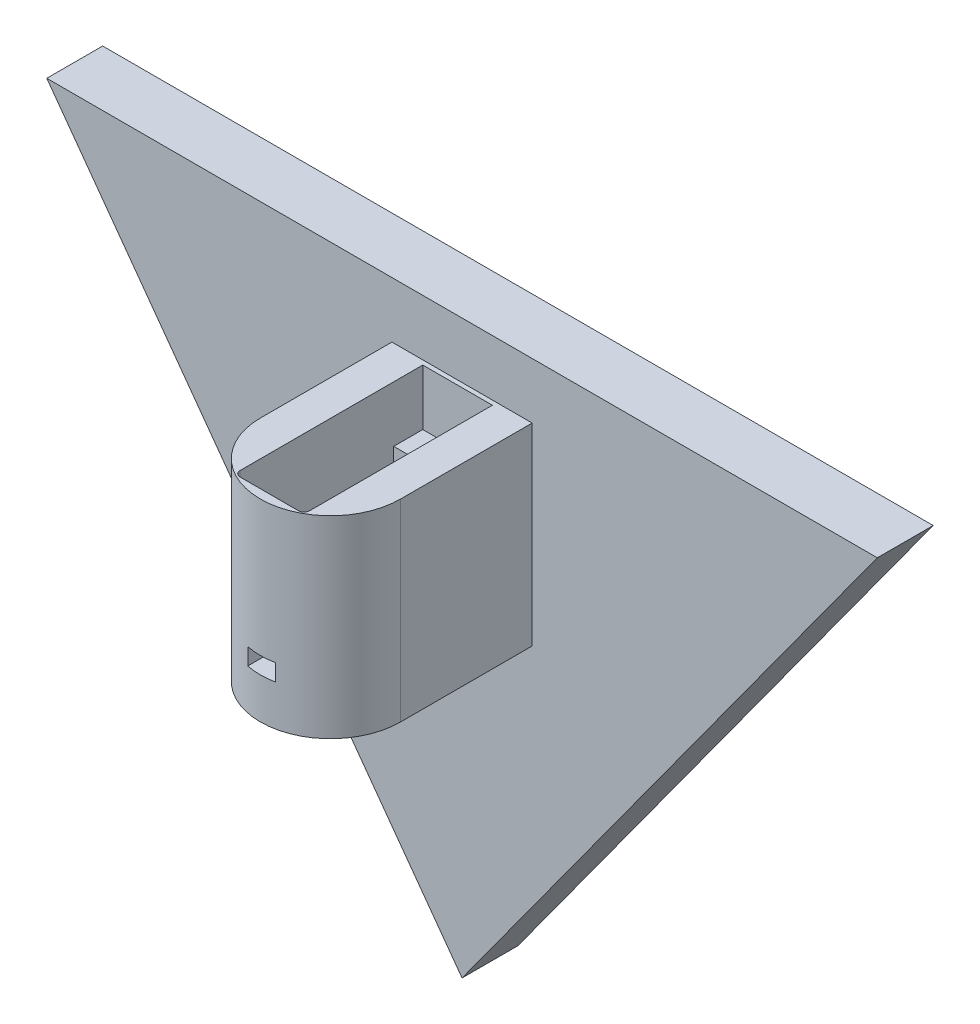
SolidWorks part; units mm, degrees
ref_plane "Front Plane" through (0, 0, 0) normal (0, 0, 1) x (1, 0, 0)
ref_plane "Top Plane" through (0, 0, 0) normal (0, 1, 0) x (1, 0, 0)
ref_plane "Right Plane" through (0, 0, 0) normal (1, 0, 0) x (0, 0, -1)
sketch "Sketch4" plane through (0, 0, 0) normal (0, 0, 1) x (1, 0, 0)
  line L0 (55, 0) -> (-55, 0) construction
  line L1 (-6.23, -9.975) -> (6.23, -9.975)
  line L2 (-6.23, -9.975) -> (-6.23, 7.275)
  line L3 (-6.23, 7.275) -> (6.23, 7.275)
  line L4 (6.23, -9.975) -> (6.23, 7.275)
  point P4 (0, 7.275)
  dimension "D1" = 12.46
  dimension "D2" = 17.25
  dimension "D3" = 9.975
extrude "Boss-Extrude3" add sketch "Sketch4" along normal blind 6
sketch "Sketch8" plane through (0, -9.975, 0) normal (0, -1, 0) x (-1, 0, 0)
  circle A0 centre (0, -23.55) radius 12.5468
  circle A1 centre (0, -23.55) radius 11.15
  dimension "D1" = 22.3
  dimension "D2" = 23.55
extrude "Boss-Extrude6" add sketch "Sketch8" along normal blind 7.3 and the other way up to surface (17.25 mm away) other way up to face at (0, 7.275, 3)
sketch "Sketch5" plane through (0, 7.275, 0) normal (0, 1, 0) x (1, 0, 0)
  line L8 (12.5468, -23.55) -> (12.5468, 0)
  line L9 (12.5468, 0) -> (6.23, 0)
  line L10 (-12.5468, -23.55) -> (-12.5468, 0)
  line L11 (-12.5468, 0) -> (-6.23, 0)
  line L12 (-6.23, 0) -> (-6.23, -29.7)
  line L14 (6.23, -29.7) -> (6.23, 0)
  line L15 (-6.23, -29.7) -> (6.23, -29.7)
  line L16 (6.23, -6) -> (-6.23, -6) construction
  circle A0 centre (0, -23.55) radius 12.5468 construction
  arc A1 (-12.5468, -23.55) -> (12.5468, -23.55) centre (0, -23.55) ccw
  dimension "D1" = 23.7
  dimension "D2" = 23.55
extrude "Boss-Extrude4" add sketch "Sketch5" against normal up to surface (17.25 mm away) up to face at (0, -9.975, 3)
sketch "Sketch6" plane through (0, 7.275, 0) normal (0, 1, 0) x (1, 0, 0)
  line L0 (6.23, -6) -> (-6.23, -6) construction
  line L3 (6.23, -29.7) -> (-6.23, -29.7) construction
  circle A0 centre (0, -3.6) radius 0.5
  circle A1 centre (0, -32.1) radius 0.5
  dimension "D1" = 1
  dimension "D3" = 1
  dimension "D2" = 2.4
  dimension "D4" = 2.4
extrude "Cut-Extrude1" cut sketch "Sketch6" against normal blind 5
chamfer "Chamfer1" distance 0.5 angle 60 2 edges at (0, 7.275, 4.1) (0, 7.275, 32.6) first distance on face at (0, 7.275, 4.1)
sketch "Sketch10" plane through (0, 7.275, 0) normal (0, 1, 0) x (1, 0, 0)
  line L1 (-6.23, -6) -> (6.23, -6)
  line L2 (-6.23, -6) -> (-6.23, -29.7)
  line L3 (-6.23, -29.7) -> (6.23, -29.7)
  line L4 (6.23, -6) -> (6.23, -29.7)
extrude "Cut-Extrude3" cut sketch "Sketch10" against normal up to surface (17.25 mm away) up to face at (0, -9.975, 27.1007)
ref_plane "Plane1" through (0, 0, 36.0968) normal (0, 0, 1) x (1, 0, 0)
sketch "Sketch11" plane through (0, 0, 36.0968) normal (0, 0, 1) x (1, 0, 0)
  line L0 (-11.15, -9.975) -> (11.15, -9.975) construction
  line L1 (-2.5, -6.975) -> (2.5, -6.975)
  line L2 (-2.5, -6.975) -> (-2.5, -9.975)
  line L3 (-2.5, -9.975) -> (2.5, -9.975)
  line L4 (2.5, -6.975) -> (2.5, -9.975)
  point P4 (0, -6.975)
  dimension "D1" = 0
  dimension "D2" = 5
  dimension "D3" = 3
extrude "Cut-Extrude4" cut sketch "Sketch11" against normal up to next
sketch "Sketch13" plane through (0, -17.275, 0) normal (0, -1, 0) x (1, 0, 0)
  line L0 (-12.5468, 23.55) -> (-12.5468, 0)
  line L1 (-12.5468, 0) -> (12.5468, 0)
  line L2 (12.5468, 0) -> (12.5468, 23.55)
  arc A0 (-12.5468, 23.55) -> (12.5468, 23.55) centre (0, 23.55) ccw
  point P3 (0, 0)
extrude "Boss-Extrude7" add sketch "Sketch13" against normal up to surface (7.3 mm away) up to face at (6.0145, -9.975, 27.3356)
sketch "Sketch15" plane through (0, 7.275, 0) normal (0, 1, 0) x (1, 0, 0)
  line L0 (-12.5468, 0) -> (12.5468, 0)
  line L1 (12.5468, 0) -> (12.5468, -23.55)
  line L2 (-12.5468, 0) -> (-12.5468, -23.55)
  line L3 (6.23, -6) -> (6.23, -29.7) construction
  line L4 (-6.23, -0.8) -> (6.23, -0.8)
  line L5 (-6.23, -0.8) -> (-6.23, -33.5)
  line L6 (-5.23, -34.5) -> (5.23, -34.5)
  line L7 (6.23, -0.8) -> (6.23, -33.5)
  arc A0 (-12.5468, -23.55) -> (12.5468, -23.55) centre (0, -23.55) ccw
  circle A1 centre (0, -3.6) radius 0.5 construction
  arc A2 (5.23, -34.5) -> (6.23, -33.5) centre (5.23, -33.5) ccw
  arc A3 (-6.23, -33.5) -> (-5.23, -34.5) centre (-5.23, -33.5) ccw
  point P15 (0, -0.8)
  dimension "D1" = 0.8
  dimension "D3" = 1
  dimension "D2" = 2.8
  dimension "D4" = 0
  dimension "D5" = 34.5
extrude "Boss-Extrude9" add sketch "Sketch15" along normal blind 10
sketch "Sketch16" plane through (0, -17.275, 0) normal (0, -1, 0) x (1, 0, 0)
  circle A0 centre (0, 23.55) radius 11.15
  circle A1 centre (0, 23.55) radius 7.15
  circle A2 centre (0, 23.55) radius 11.15 construction
  dimension "D1" = 14.3
extrude "Boss-Extrude10" add sketch "Sketch16" against normal up to surface (7.3 mm away) up to face at (6.0145, -9.975, 27.3356)
sketch "Sketch17" plane through (0, -17.275, 0) normal (0, -1, 0) x (1, 0, 0)
  circle A0 centre (0, 23.55) radius 10.15
  circle A1 centre (0, 23.55) radius 7.15
  circle A2 centre (0, 23.55) radius 7.15 construction
  dimension "D1" = 20.3
extrude "Cut-Extrude5" cut sketch "Sketch17" against normal blind 1.3
sketch "Sketch1" plane through (0, 0, 0) normal (0, 0, 1) x (1, 0, 0)
  line L0 (0, -75) -> (74.3071, 27.275)
  line L1 (74.3071, 27.275) -> (-74.3071, 27.275)
  line L2 (-74.3071, 27.275) -> (0, -75)
  line L3 (6.23, 17.275) -> (-6.23, 17.275) construction
  line L4 (13.8015, 0) -> (-13.8015, 0) construction
  point P10 (0, 27.275)
  dimension "D2" = 10
  dimension "D1" = 72
  dimension "D3" = 75
extrude "Offset R" add sketch "Sketch1" against normal blind 10 contours L2 L0 L1
